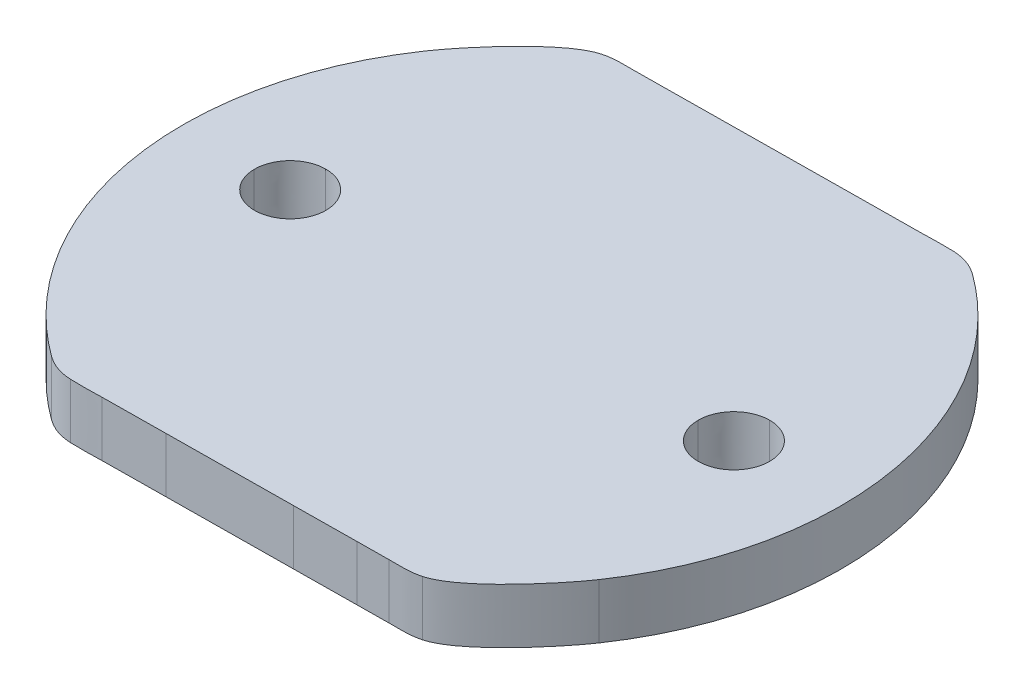
SolidWorks part; units mm, degrees
ref_plane "Front Plane" through (0, 0, 0) normal (0, 0, 1) x (1, 0, 0)
ref_plane "Top Plane" through (0, 0, 0) normal (0, 1, 0) x (1, 0, 0)
ref_plane "Right Plane" through (0, 0, 0) normal (1, 0, 0) x (0, 0, -1)
sketch "Sketch1" plane through (0, 0, 0) normal (0, 1, 0) x (1, 0, 0)
  line L0 (60.8717, 62.8884) -> (60.8717, 62.8915)
  spline S0 degree 3 poles (59.597, 32.3955) (59.6175, 30.1217) (61.4849, 28.2889) (63.7656, 28.3165) knots 0 0 0 0 1 1 1 1
  spline S1 degree 3 poles (63.7656, 28.3165) (66.0462, 28.3365) (67.8721, 30.2044) (67.8515, 32.4851) knots 0 0 0 0 1 1 1 1
  spline S2 degree 3 poles (67.8515, 32.4851) (67.831, 34.7588) (65.9635, 36.5916) (63.6829, 36.5709) knots 0 0 0 0 1 1 1 1
  spline S3 degree 3 poles (63.6829, 36.5709) (61.4022, 36.5409) (59.5695, 34.6761) (59.597, 32.3955) knots 0 0 0 0 1 1 1 1
  spline S4 degree 3 poles (17.057, 31.9683) (17.0776, 29.6876) (15.2449, 27.8204) (12.9711, 27.7997) knots 0 0 0 0 1 1 1 1
  spline S5 degree 3 poles (12.9711, 27.7997) (10.6904, 27.7747) (8.8232, 29.605) (8.8025, 31.8856) knots 0 0 0 0 1 1 1 1
  spline S6 degree 3 poles (8.8025, 31.8856) (8.775, 34.1594) (10.6078, 36.0266) (12.8884, 36.0542) knots 0 0 0 0 1 1 1 1
  spline S7 degree 3 poles (12.8884, 36.0542) (15.1622, 36.0742) (17.0294, 34.2489) (17.057, 31.9683) knots 0 0 0 0 1 1 1 1
  spline S8 degree 3 poles (60.8717, 62.8915) (59.8244, 63.6632) (58.7702, 64.0421) (57.468, 64.1179) knots 0 0 0 0 1 1 1 1
  spline S9 degree 3 poles (57.468, 64.1179) (56.2484, 64.1799) (55.0357, 64.1029) (53.823, 64.0879) knots 0 0 0 0 1 1 1 1
  spline S10 degree 3 poles (53.823, 64.0879) (51.3908, 64.0629) (48.9586, 64.0379) (46.5263, 64.0189) knots 0 0 0 0 1 1 1 1
  spline S11 degree 3 poles (46.5263, 64.0189) (41.6618, 63.9639) (36.7974, 63.9154) (31.9329, 63.8674) knots 0 0 0 0 1 1 1 1
  spline S12 degree 3 poles (31.9329, 63.8674) (29.4938, 63.8374) (27.0615, 63.8174) (24.6293, 63.7914) knots 0 0 0 0 1 1 1 1
  spline S13 degree 3 poles (24.6293, 63.7914) (23.4097, 63.7764) (22.1971, 63.7714) (20.9775, 63.7564) knots 0 0 0 0 1 1 1 1
  spline S14 degree 3 poles (20.9775, 63.7564) (19.7579, 63.7414) (18.559, 63.8389) (17.3464, 63.5084) knots 0 0 0 0 1 1 1 1
  spline S15 degree 3 poles (17.3464, 63.5084) (13.8599, 62.5576) (8.5751, 56.1841) (6.825, 53.6141) knots 0 0 0 0 1 1 1 1
  spline S16 degree 3 poles (6.825, 53.6141) (-4.716, 36.6573) (-0.7611, 13.6097) (15.7754, 1.4691) knots 0 0 0 0 1 1 1 1
  spline S17 degree 3 poles (15.7754, 1.4691) (16.8296, 0.6974) (17.8769, 0.3185) (19.186, 0.2496) knots 0 0 0 0 1 1 1 1
  spline S18 degree 3 poles (19.186, 0.2496) (20.3987, 0.1806) (21.6114, 0.2546) (22.8309, 0.2696) knots 0 0 0 0 1 1 1 1
  spline S19 degree 3 poles (22.8309, 0.2696) (25.2563, 0.2946) (27.6954, 0.3196) (30.1277, 0.3456) knots 0 0 0 0 1 1 1 1
  spline S20 degree 3 poles (30.1277, 0.3456) (34.9921, 0.3956) (39.8566, 0.4421) (44.7211, 0.4901) knots 0 0 0 0 1 1 1 1
  spline S21 degree 3 poles (44.7211, 0.4901) (47.1533, 0.5201) (49.5856, 0.5401) (52.0247, 0.5661) knots 0 0 0 0 1 1 1 1
  spline S22 degree 3 poles (52.0247, 0.5661) (53.2374, 0.5811) (54.4569, 0.5961) (55.6696, 0.6011) knots 0 0 0 0 1 1 1 1
  spline S23 degree 3 poles (55.6696, 0.6011) (56.8892, 0.6161) (58.088, 0.5186) (59.3076, 0.8491) knots 0 0 0 0 1 1 1 1
  spline S24 degree 3 poles (59.3076, 0.8491) (62.7941, 1.7999) (68.0788, 8.1803) (69.822, 10.7434) knots 0 0 0 0 1 1 1 1
  spline S25 degree 3 poles (69.822, 10.7434) (81.3631, 27.7002) (77.4082, 50.7479) (60.8717, 62.8884) knots 0 0 0 0 1 1 1 1
extrude "Boss-Extrude1" add sketch "Sketch1" along normal blind 6.35
sketch "Sketch2" plane through (0, 6.35, 0) normal (0, 1, 0) x (1, 0, 0)
  line L0 (12.9338, 31.931) -> (63.7307, 32.4501) construction
  circle A0 centre (12.9338, 31.931) radius 4.1234 construction
  circle A1 centre (63.7307, 32.4501) radius 4.1209 construction
  spline S0 degree 3 poles (12.8884, 36.0542) (10.6078, 36.0266) (8.775, 34.1594) (8.8025, 31.8856) knots 0 0 0 0 1 1 1 1 construction
  spline S1 degree 3 poles (12.9711, 27.7997) (15.2449, 27.8204) (17.0776, 29.6876) (17.057, 31.9683) knots 0 0 0 0 1 1 1 1 construction
  spline S4 degree 3 poles (67.8515, 32.4851) (67.831, 34.7588) (65.9635, 36.5916) (63.6829, 36.5709) knots 0 0 0 0 1 1 1 1 construction
  spline S5 degree 3 poles (63.6829, 36.5709) (61.4022, 36.5409) (59.5695, 34.6761) (59.597, 32.3955) knots 0 0 0 0 1 1 1 1 construction
  point P12 (38.3322, 32.1905)
